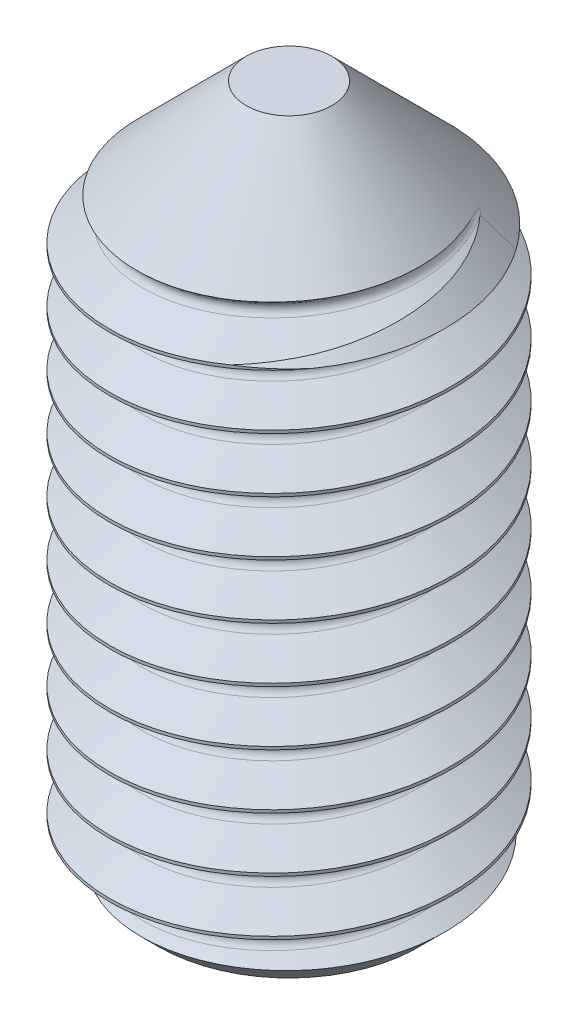
SolidWorks part; units mm, degrees
ref_plane "Front Plane" through (0, 0, 0) normal (0, 0, 1) x (1, 0, 0)
ref_plane "Top Plane" through (0, 0, 0) normal (0, 1, 0) x (1, 0, 0)
ref_plane "Right Plane" through (0, 0, 0) normal (1, 0, 0) x (0, 0, -1)
sketch "Sketch1" plane through (0, 0, 0) normal (0, 1, 0) x (1, 0, 0)
  circle A0 centre (0, 0) radius 2.5
  dimension "D1" = 5
extrude "Boss-Extrude1" add sketch "Sketch1" along normal mid plane 10
sketch "Sketch2" plane through (0, 0, 0) normal (0, 0, 1) x (1, 0, 0)
  line L0 (0.625, 5) -> (4.7582, 0.8668)
  line L1 (4.7582, 0.8668) -> (4.7582, -2.1418)
  line L2 (4.7582, -2.1418) -> (1.9, -5)
  line L3 (1.9, -5) -> (1.9, -8.246)
  line L4 (1.9, -8.246) -> (9.4714, -8.246)
  line L5 (9.4714, -8.246) -> (9.4714, 9.6919)
  line L6 (9.4714, 9.6919) -> (0.625, 9.6919)
  line L7 (0.625, 9.6919) -> (0.625, 5)
  line L8 (0, 0) -> (0, -3.1523) construction
  line L9 (2.5, 5) -> (-2.5, 5) construction
  line L10 (-2.5, -5) -> (2.5, -5) construction
  dimension "D1" = 1.25
  dimension "D2" = 3.8
  dimension "D3" = 135
  dimension "D4" = 135
revolve "Cut-Revolve1" cut sketch "Sketch2" angle 360 about L8
sketch "Sketch3" plane through (0, -5, 0) normal (0, -1, 0) x (1, 0, 0)
  line L1 (1.275, -0.7361) -> (1.275, 0.7361)
  line L2 (1.275, 0.7361) -> (0, 1.4722)
  line L3 (0, 1.4722) -> (-1.275, 0.7361)
  line L4 (-1.275, 0.7361) -> (-1.275, -0.7361)
  line L5 (-1.275, -0.7361) -> (0, -1.4722)
  line L6 (0, -1.4722) -> (1.275, -0.7361)
  circle A0 centre (0, 0) radius 1.275 construction
  dimension "D1" = 2.55
extrude "Cut-Extrude1" cut sketch "Sketch3" against normal blind 2.5
sketch "Sketch4" plane through (0, -5, 0) normal (0, -1, 0) x (1, 0, 0)
  circle A0 centre (0, 0) radius 2.5 construction
  circle A1 centre (0, 0) radius 2.5
curve "Helix/Spiral1" pitch 0.8 height 13.4 radius 2.5 centre (0, -5, 0) axis (0, 1, 0) start towards (0, 0, -1)
sketch "Sketch5" plane through (0, 0, 0) normal (0, 0, 1) x (1, 0, 0)
  line L1 (2.5363, -4.7663) -> (2.0175, -5.0659)
  line L2 (2.0175, -5.2658) -> (2.5363, -5.5653)
  line L3 (2.5363, -5.5653) -> (2.5363, -4.7663)
  circle A0 centre (2.3056, -5.1658) radius 0.2307 construction
  arc A1 (2.0175, -5.0659) -> (2.0175, -5.2658) centre (2.0752, -5.1658) ccw
  dimension "D2" = 0.1154
  dimension "D1" = 0.799
sweep "Cut-Sweep1" cut profiles "Sketch5" path "Helix/Spiral1" align with end faces yes
sketch "Sketch6" plane through (0, -5, 0) normal (0, -1, 0) x (1, 0, 0)
  circle A0 centre (0, 0) radius 1.4722
extrude "Cut-Extrude2" cut sketch "Sketch6" against normal blind 1 draft 75
